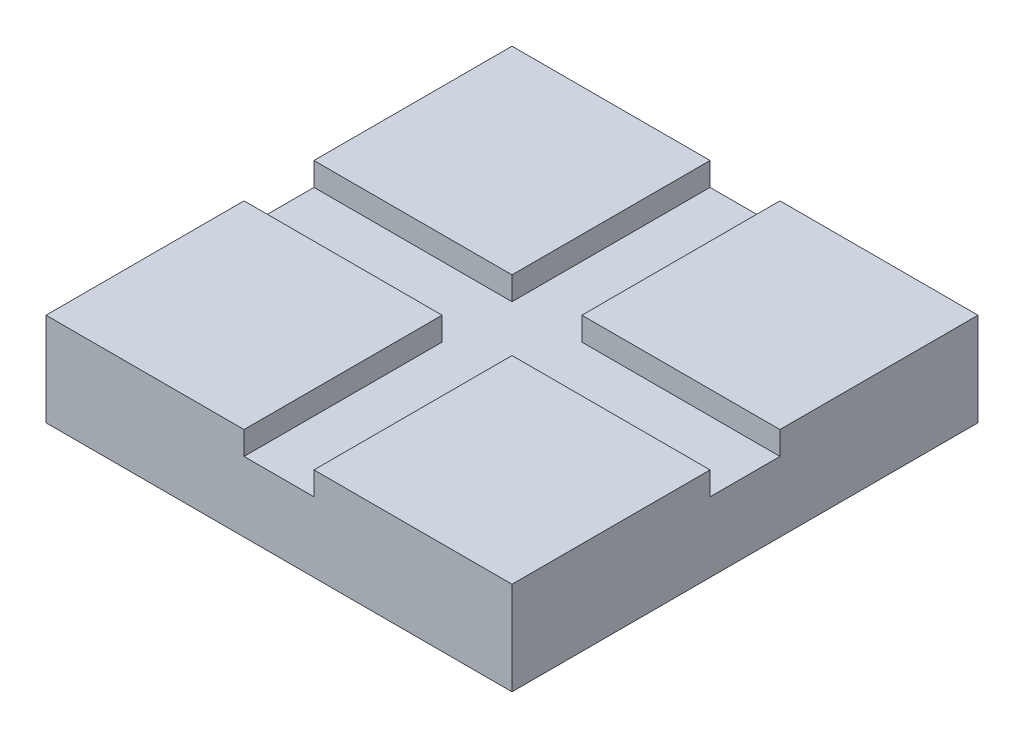
SolidWorks part; units mm, degrees
ref_plane "Plano frontal" through (0, 0, 0) normal (0, 0, 1) x (1, 0, 0)
ref_plane "Plano superior" through (0, 0, 0) normal (0, 1, 0) x (1, 0, 0)
ref_plane "Plano direito" through (0, 0, 0) normal (1, 0, 0) x (0, 0, -1)
sketch "Esboço2" plane through (0, 0, 0) normal (0, 1, 0) x (1, 0, 0)
  line L0 (7.5, 7.5) -> (50, 7.5)
  line L1 (-50, -50) -> (50, -50)
  line L2 (-50, -50) -> (-50, 50)
  line L3 (-50, 50) -> (50, 50)
  line L4 (50, -50) -> (50, 50)
  line L5 (-50, -50) -> (50, 50) construction
  line L6 (-50, 50) -> (50, -50) construction
  line L7 (7.5, -50) -> (-7.5, -50)
  line L8 (7.5, -50) -> (7.5, -7.5)
  line L9 (7.5, 50) -> (-7.5, 50)
  line L10 (-7.5, -50) -> (-7.5, -7.5)
  line L11 (7.5, -50) -> (-7.5, 50) construction
  line L12 (7.5, 50) -> (-7.5, -50) construction
  line L13 (-50, -7.5) -> (-7.5, -7.5)
  line L14 (-50, -7.5) -> (-50, 7.5)
  line L15 (-50, 7.5) -> (-7.5, 7.5)
  line L16 (50, -7.5) -> (50, 7.5)
  line L17 (-50, -7.5) -> (50, 7.5) construction
  line L18 (-50, 7.5) -> (50, -7.5) construction
  line L19 (7.5, 7.5) -> (7.5, 50)
  line L20 (7.5, -7.5) -> (50, -7.5)
  line L21 (-7.5, 7.5) -> (-7.5, 50)
  point P0 (0, 0)
  point P5 (0, 0)
  point P11 (0, 0)
  point P16 (0, 50)
  point P17 (0, 50)
  point P18 (50, 0)
  point P19 (50, 0)
  dimension "D1" = 100
  dimension "D2" = 15
  dimension "D3" = 15
extrude "Ressalto-extrusão1" add sketch "Esboço2" along normal blind 20 contours L15 L21 L3 L2 | L19 L0 L4 L3 | L13 L2 L1 L10 | L20 L8 L1 L4 region at (28.75, 0, -28.75) region at (28.75, 0, 28.75) region at (-28.75, 0, -28.75) region at (-28.75, 0, 28.75)
extrude "Ressalto-extrusão2" add sketch "Esboço2<3>" along normal blind 15 contours L21 L15 L2 L13 L10 L1 L8 L20 L4 L0 L19 L3 region at (0, 0, 0)
sketch "Esboço2<3>" plane through (0, 0, 0) normal (0, 1, 0) x (1, 0, 0) same geometry as "Esboço2"
